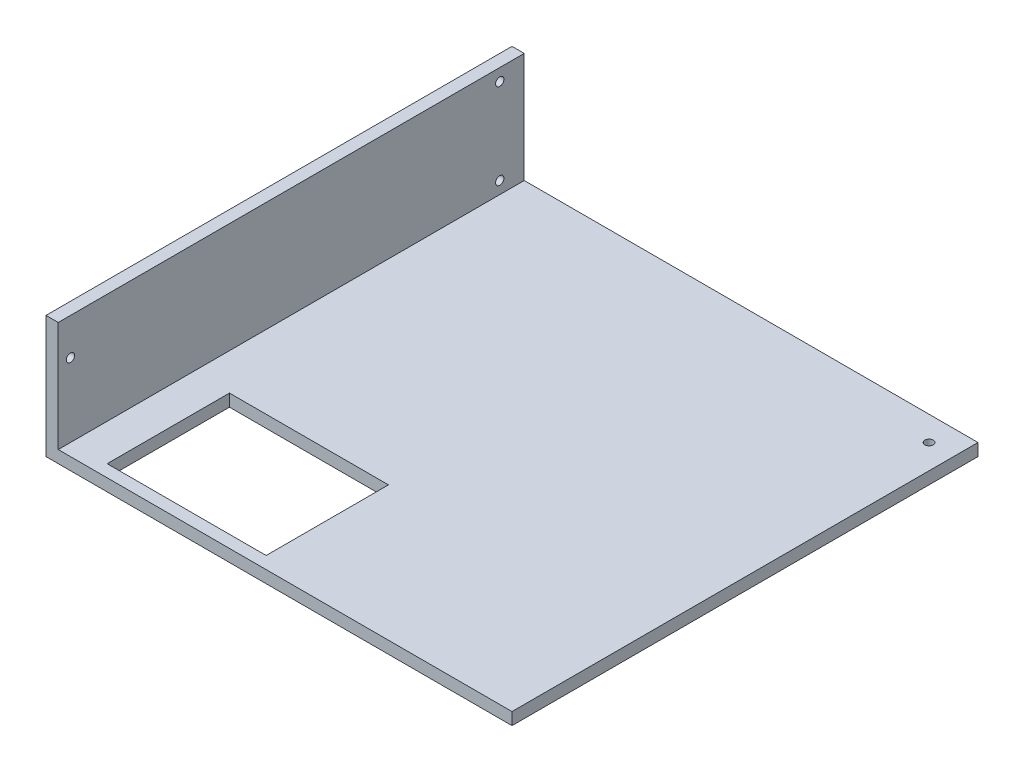
SolidWorks part; units mm, degrees
ref_plane "Front Plane" through (0, 0, 0) normal (0, 0, 1) x (1, 0, 0)
ref_plane "Top Plane" through (0, 0, 0) normal (0, 1, 0) x (1, 0, 0)
ref_plane "Right Plane" through (0, 0, 0) normal (1, 0, 0) x (0, 0, -1)
sketch "Sketch1" plane through (0, 0, 0) normal (0, 1, 0) x (1, 0, 0)
  line L1 (-95.25, 95.25) -> (95.25, 95.25)
  line L2 (-95.25, 95.25) -> (-95.25, -95.25)
  line L3 (-95.25, -95.25) -> (95.25, -95.25)
  line L4 (95.25, 95.25) -> (95.25, -95.25)
  line L5 (-95.25, 95.25) -> (95.25, -95.25) construction
  line L6 (-95.25, -95.25) -> (95.25, 95.25) construction
  point P0 (0, 0)
  dimension "D1" = 190.5
  dimension "D2" = 190.5
extrude "Boss-Extrude1" add sketch "Sketch1" along normal blind 5
sketch "Sketch2" plane through (0, 5, 0) normal (0, 1, 0) x (1, 0, 0)
  line L0 (-95.25, -95.25) -> (95.25, -95.25) construction
  line L1 (-95.25, 95.25) -> (-90.25, 95.25)
  line L2 (-95.25, 95.25) -> (-95.25, -95.25)
  line L3 (-95.25, -95.25) -> (-90.25, -95.25)
  line L4 (-90.25, 95.25) -> (-90.25, -95.25)
  dimension "D1" = 5
extrude "Boss-Extrude2" add sketch "Sketch2" along normal blind 45
sketch "Sketch6" plane through (0, 0, 0) normal (0, -1, 0) x (1, 0, 0)
  line L1 (-10.25, 90.25) -> (-75.25, 90.25)
  line L2 (-10.25, 90.25) -> (-10.25, 40.25)
  line L3 (-10.25, 40.25) -> (-75.25, 40.25)
  line L4 (-75.25, 90.25) -> (-75.25, 40.25)
  line L6 (-95.25, -95.25) -> (-95.25, 95.25) construction
  line L7 (-95.25, 95.25) -> (95.25, 95.25) construction
  dimension "D1" = 50
  dimension "D2" = 65
  dimension "D3" = 20
  dimension "D4" = 5
extrude "Cut-Extrude2" cut sketch "Sketch6" against normal up to surface (5 mm away) up to face at (2.5, 5, 0)
sketch "Sketch7" plane through (-95.25, 0, 0) normal (-1, 0, 0) x (0, 0, 1)
  line L1 (-95.25, 50) -> (95.25, 50) construction
  line L2 (-95.25, 0) -> (95.25, 0) construction
  line L3 (-95.25, 50) -> (-95.25, 0) construction
  line L5 (95.25, 50) -> (95.25, 0) construction
  circle A0 centre (90.25, 35) radius 1.7
  circle A1 centre (-85.25, 45) radius 1.7
  circle A2 centre (-85.25, 10) radius 1.7
  dimension "D1" = 3.4
  dimension "D4" = 10
  dimension "D2" = 5
  dimension "D3" = 15
  dimension "D5" = 5
  dimension "D6" = 10
extrude "Cut-Extrude3" cut sketch "Sketch7" against normal up to surface (5 mm away) up to face at (-90.25, 27.5, 0)
sketch "Sketch9" plane through (0, 0, 0) normal (0, -1, 0) x (1, 0, 0)
  line L0 (95.25, -95.25) -> (-95.25, -95.25) construction
  line L1 (95.25, 95.25) -> (95.25, -95.25) construction
  circle A0 centre (85.25, -85.25) radius 1.7
  dimension "D3" = 3.4
  dimension "D1" = 10
  dimension "D2" = 10
extrude "Cut-Extrude4" cut sketch "Sketch9" against normal up to surface (5 mm away) up to face at (-42.75, 5, 65.25)
sketch "Sketch10" plane through (0, 0, 0) normal (0, -1, 0) x (1, 0, 0)
  circle A0 centre (85.25, -85.25) radius 2.2
  dimension "D1" = 4.4
extrude "Cut-Extrude5" cut sketch "Sketch10" against normal blind 2
sketch "Sketch11" plane through (-95.25, 0, 0) normal (-1, 0, 0) x (0, 0, 1)
  circle A0 centre (-85.25, 10) radius 2.2
  circle A2 centre (90.25, 35) radius 2.2
  circle A4 centre (-85.25, 45) radius 2.2
  dimension "D1" = 4.4
  dimension "D2" = 4.4
extrude "Cut-Extrude6" cut sketch "Sketch11" against normal blind 2
